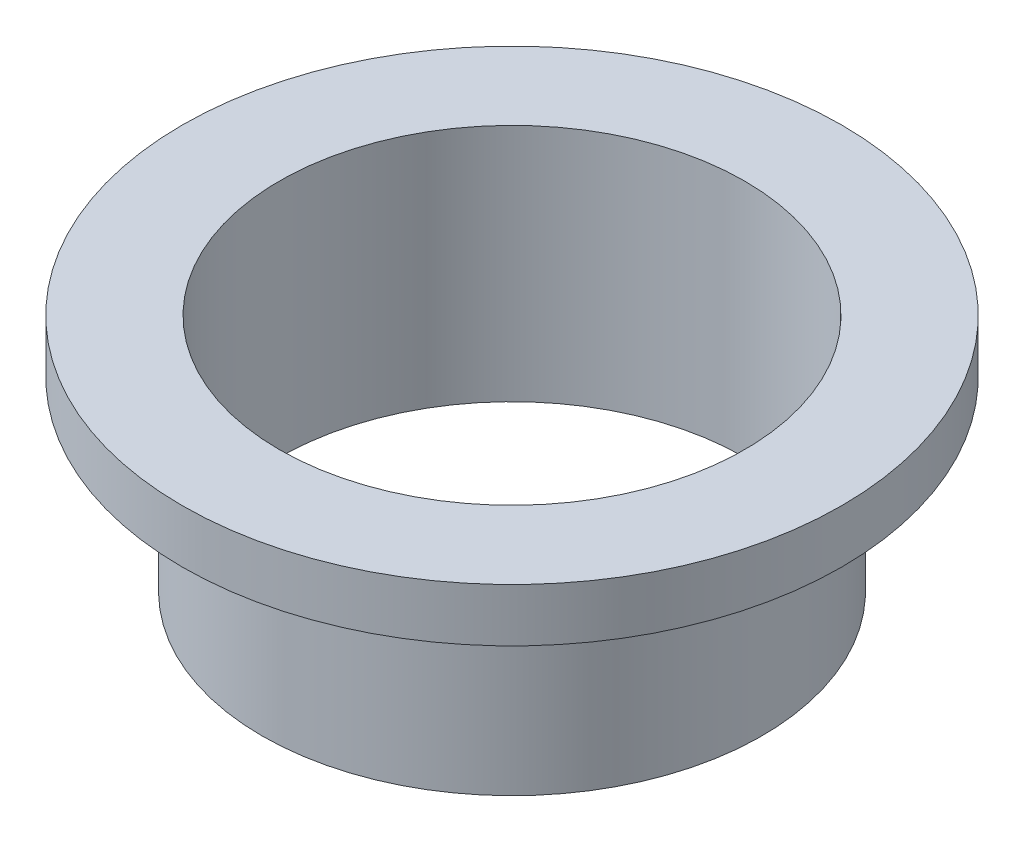
SolidWorks part; units mm, degrees
ref_plane "Front Plane" through (0, 0, 0) normal (0, 0, 1) x (1, 0, 0)
ref_plane "Top Plane" through (0, 0, 0) normal (0, 1, 0) x (1, 0, 0)
ref_plane "Right Plane" through (0, 0, 0) normal (1, 0, 0) x (0, 0, -1)
sketch "Sketch1" plane through (0, 0, 0) normal (0, 1, 0) x (1, 0, 0)
  circle A0 centre (0, 0) radius 8.75
  circle A1 centre (0, 0) radius 9.4
  circle A2 centre (0, 0) radius 12.4
  dimension "D1" = 18.8
  dimension "D2" = 17.5
  dimension "D3" = 3
extrude "Boss-Extrude1" add sketch "Sketch1" along normal blind 2 contours A2 A1 | A1 A0 region at (-9.1341, 0, 0) region at (-12.0493, 0, 0)
extrude "Boss-Extrude2" add sketch "Sketch1<3>" against normal blind 7 contours A1 A0 region at (-9.1341, 0, 0)
sketch "Sketch1<3>" plane through (0, 0, 0) normal (0, 1, 0) x (1, 0, 0) same geometry as "Sketch1"
